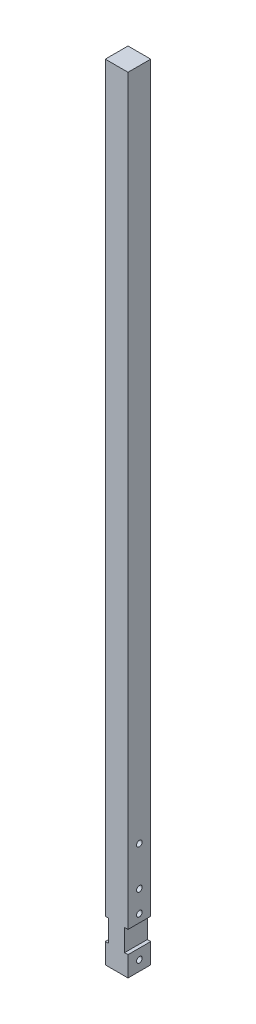
SolidWorks part; units mm, degrees
material "Alliage 1060"
ref_plane "Plan de face" through (0, 0, 0) normal (0, 0, 1) x (1, 0, 0)
ref_plane "Plan de dessus" through (0, 0, 0) normal (0, 1, 0) x (1, 0, 0)
ref_plane "Plan de droite" through (0, 0, 0) normal (1, 0, 0) x (0, 0, -1)
sketch "Esquisse1" plane through (0, 0, 0) normal (0, 1, 0) x (1, 0, 0)
  line L0 (-5, 5) -> (5, -5) construction
  line L1 (-5, 5) -> (5, 5)
  line L2 (-5, 5) -> (-5, -5)
  line L3 (-5, -5) -> (5, -5)
  line L4 (5, 5) -> (5, -5)
  dimension "D1" = 10
extrude "Boss.-Extru.1" add sketch "Esquisse1" along normal up to surface (345 mm away)
hole_wizard "Trou taraudé M3x0.51" positions "Esquisse2" profile "Esquisse3" tap size "M3x0.5" standard "Ansi Metric" end condition through all
sketch "Esquisse2" plane through (-5, 0, 0) normal (-1, 0, 0) x (0, 0, 1)
  line L0 (0, 50.3) -> (0, 47.1) construction
  line L1 (-2.6, 50.3) -> (2.9, 50.3) construction
  line L2 (2.9, 47.1) -> (-2.6, 47.1) construction
  line L6 (0, 33.1) -> (0, 29.9) construction
  line L7 (2.9, 29.9) -> (-2.6, 29.9) construction
  line L8 (-2.6, 33.1) -> (2.9, 33.1) construction
  circle A0 centre (0, 22) radius 3 construction
  circle A1 centre (0, 4.45) radius 3 construction
  point P0 (0, 22)
  point P3 (0, 4.45)
  point P6 (0, 31.5)
  point P8 (0, 48.7)
sketch "Esquisse3" plane through (-5, 22, 0) normal (0, 1, 0) x (0, 0, 1)
  line L0 (0, 0) -> (0, 10)
  line L1 (0, 10) -> (1.25, 10)
  line L2 (1.25, 10) -> (1.25, 0)
  line L5 (1.25, 0) -> (0, 0)
  line L11 (0, -6.35) -> (0, 107.95) construction
  dimension "Diamètre du trou pour taraudage jusqu'au prochain" = 2.5
  dimension "Profondeur du trou pour taraudage jusqu'au prochain" = 10
cosmetic thread "Filetage de perçage1" parameters "D2"=3
cosmetic thread "Filetage de perçage2" parameters "D2"=3
cosmetic thread "Filetage de perçage3" parameters "D2"=3
cosmetic thread "Filetage de perçage4" parameters "D2"=3
sketch "Esquisse4" plane through (0, 0, -5) normal (0, 0, -1) x (-1, 0, 0)
  line L0 (5, 345) -> (5, 0) construction
  line L1 (5, 18.5) -> (3.5, 18.5)
  line L2 (5, 18.5) -> (5, 8.9)
  line L3 (5, 8.9) -> (3.5, 8.9)
  line L4 (3.5, 18.5) -> (3.5, 8.9)
  line L5 (-3.5, 18.5) -> (-5, 18.5)
  line L6 (-3.5, 18.5) -> (-3.5, 8.9)
  line L7 (-3.5, 8.9) -> (-5, 8.9)
  line L8 (-5, 18.5) -> (-5, 8.9)
  line L9 (5, 18.5) -> (7.6438, 18.5) construction
  line L10 (5, 8.9) -> (8.1439, 8.9) construction
  line L11 (-5, 345) -> (-5, 0) construction
  dimension "D1" = 1.5
extrude "Enlèv. mat.-Extru.1" cut sketch "Esquisse4" against normal through all
